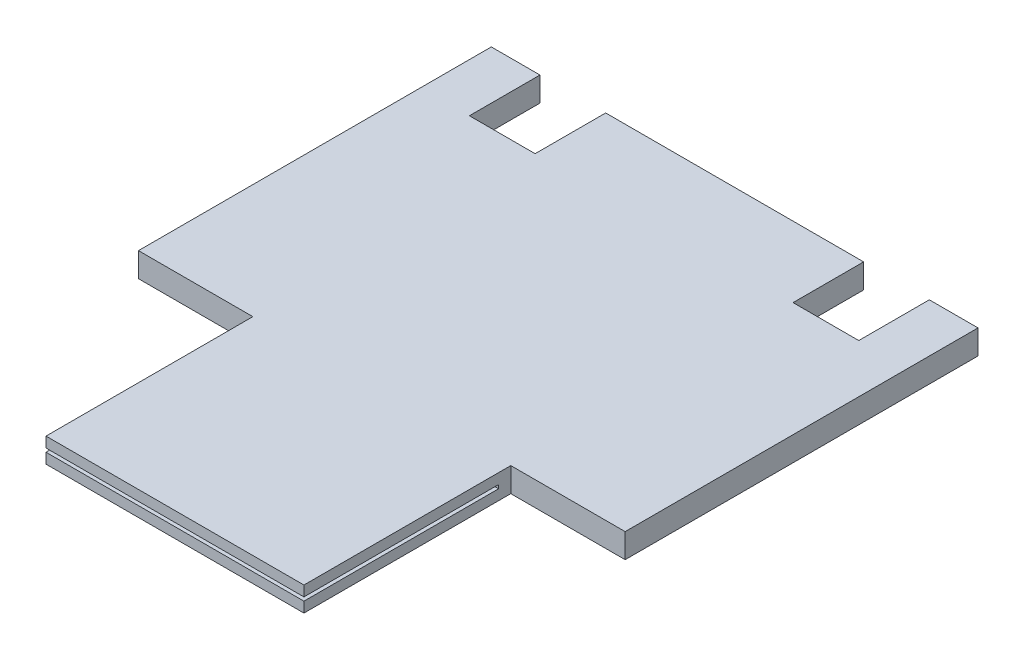
SolidWorks part; units mm, degrees
ref_plane "Front Plane" through (0, 0, 0) normal (0, 0, 1) x (1, 0, 0)
ref_plane "Top Plane" through (0, 0, 0) normal (0, 1, 0) x (1, 0, 0)
ref_plane "Right Plane" through (0, 0, 0) normal (1, 0, 0) x (0, 0, -1)
sketch "Sketch4" plane through (0, 0, 0) normal (0, 1, 0) x (1, 0, 0)
  line L1 (-53, -85) -> (53, -85)
  line L2 (-53, -85) -> (-53, 85)
  line L3 (-53, 85) -> (53, 85)
  line L4 (53, -85) -> (53, 85)
  line L5 (-53, -85) -> (53, 85) construction
  line L6 (-53, 85) -> (53, -85) construction
  point P0 (0, 0)
  dimension "D1" = 106
  dimension "D2" = 170
extrude "Boss-Extrude4" add sketch "Sketch4" along normal blind 10
sketch "Sketch6" plane through (0, 0, 85) normal (0, 0, 1) x (1, 0, 0)
  line L0 (53, 10) -> (53, 0) construction
  line L1 (-53, 0) -> (53, 0)
  line L2 (-53, 0) -> (-53, 10)
  line L3 (-53, 10) -> (53, 10)
  line L4 (53, 0) -> (53, 10)
  line L5 (0, 0) -> (0, 10) construction
  line L7 (-53, 4.25) -> (53, 4.25)
  line L8 (-53, 4.25) -> (-53, 5.75)
  line L9 (-53, 5.75) -> (53, 5.75)
  line L10 (53, 4.25) -> (53, 5.75)
  line L11 (-53, 4.25) -> (53, 5.75) construction
  line L12 (-53, 5.75) -> (53, 4.25) construction
  point P9 (0, 5)
  dimension "D1" = 10
  dimension "D2" = 1.5
extrude "Cut-Extrude2" cut sketch "Sketch6" against normal blind 80 contours L9 L2 L7 L4 region at (0, 5, 85)
sketch "Sketch7" plane through (0, 0, -85) normal (0, 0, -1) x (-1, 0, 0)
  line L1 (-53, 10) -> (53, 10)
  line L2 (-53, 10) -> (-53, 0)
  line L3 (-53, 0) -> (53, 0)
  line L4 (53, 10) -> (53, 0)
extrude "Boss-Extrude5" add sketch "Sketch7" along normal blind 60
sketch "Sketch10" plane through (0, 10, 0) normal (0, 1, 0) x (1, 0, 0)
  line L0 (0, 145) -> (0, 65) construction
  line L1 (-53, 145) -> (53, 145) construction
  line L2 (-53, 145) -> (-53, -85) construction
  line L3 (-53, 116) -> (-80, 116)
  line L4 (-53, 116) -> (-53, 0)
  line L5 (-53, 0) -> (-80, 0)
  line L6 (-80, 116) -> (-80, 0)
  line L7 (53, 0) -> (80, 0)
  line L8 (80, 116) -> (80, 0)
  line L9 (53, 116) -> (80, 116)
  line L10 (53, 116) -> (53, 0)
  line L11 (80, 196) -> (100, 196)
  line L12 (-80, 0) -> (-100, 0)
  line L13 (-80, 0) -> (-80, 196)
  line L14 (-80, 196) -> (-100, 196)
  line L15 (-100, 0) -> (-100, 196)
  line L16 (100, 0) -> (100, 196)
  line L17 (80, 0) -> (100, 0)
  line L18 (80, 0) -> (80, 196)
  line M18 (53, -85) -> (53, 145)
  line M20 (-53, 145) -> (-53, -85)
  dimension "D1" = 80
  dimension "D2" = 160
  dimension "D3" = 20
extrude "Boss-Extrude7" add sketch "Sketch10" against normal up to surface (10 mm away) contours L18 L8 L17 L16 L11 | L9 L7 L8 M18 | L3 L6 L5 M20 | L15 L12 L6 L13 L14 region at (-66.5, 10, -58) region at (-90, 10, -98) region at (66.5, 10, -58) region at (90, 10, -98) up to face at (0, 0, -30)
sketch "Sketch11" plane through (-100, 0, 0) normal (-1, 0, 0) x (0, 0, 1)
  line L0 (0, 0) -> (-196, 0) construction
  line L1 (-196, 10) -> (-145, 10)
  line L2 (-196, 10) -> (-196, 0)
  line L3 (-196, 0) -> (-145, 0)
  line L4 (-145, 10) -> (-145, 0)
  dimension "D1" = 51
extrude "Cut-Extrude3" cut sketch "Sketch11" against normal through all
